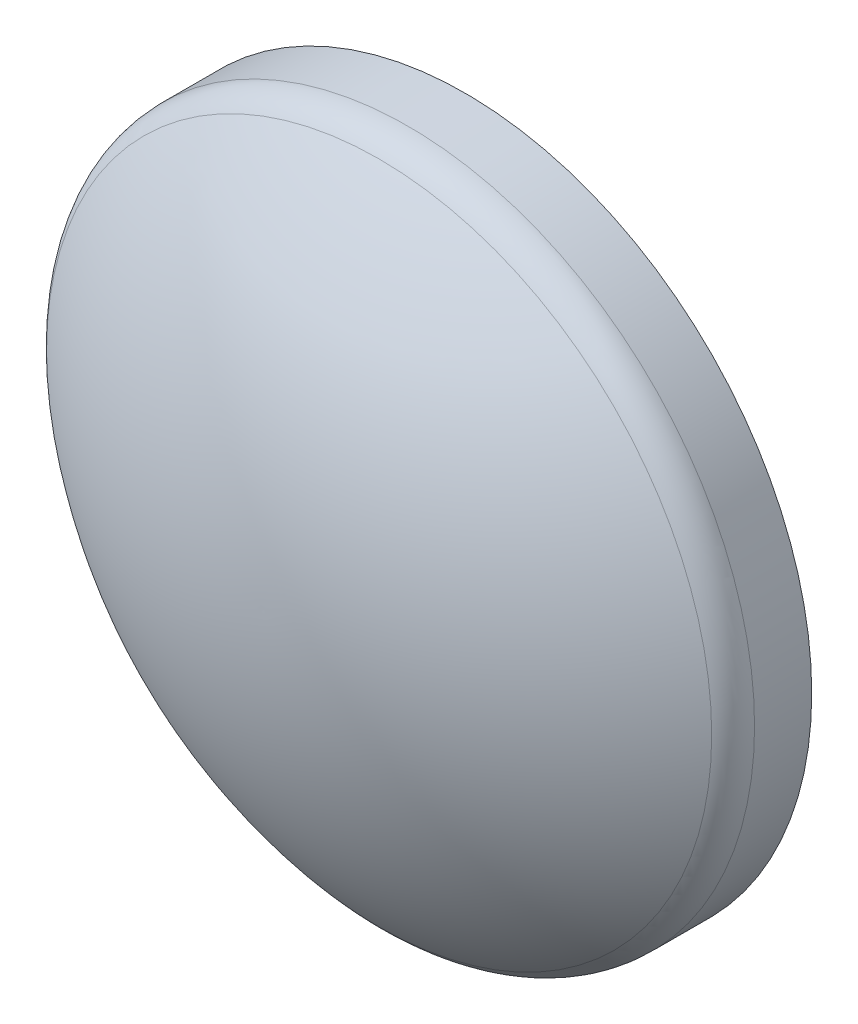
SolidWorks part; units mm, degrees
material "ASTM A240 304H"
ref_plane "Front Plane" through (0, 0, 0) normal (0, 0, 1) x (1, 0, 0)
ref_plane "Top Plane" through (0, 0, 0) normal (0, 1, 0) x (1, 0, 0)
ref_plane "Right Plane" through (0, 0, 0) normal (1, 0, 0) x (0, 0, -1)
ref_axis "Axis1" through (0, 0, -88.99) along (0, 0, 1)
ref_plane "Plane1" through (0, 0, 0) normal (1, 0, 0) x (0, 0, -1)
sketch "Sketch1" plane through (0, 0, 0) normal (1, 0, 0) x (0, 0, -1)
  line L0 (-12.7, 0) -> (12.7, 0) construction
  line L2 (-12.7, 215.011) -> (12.7, 215.011)
  line L3 (-12.7, 215.011) -> (-12.7, 230.886)
  line L4 (-12.7, 230.886) -> (12.7, 230.886)
  line L5 (12.7, 215.011) -> (12.7, 230.886)
  dimension "D1" = 215.011
  dimension "WIDTH" = 25.4
  dimension "THK" = 15.875
revolve "Revolve1" add sketch "Sketch1" angle 360 mid plane about L0
sketch "Sketch3" plane through (0, 0, 12.7) normal (0, 0, 1) x (1, 0, 0)
  circle A0 centre (0, 0) radius 230.886
  dimension "D1" = 461.772
sketch "Sketch4" plane through (0, 0, 0) normal (1, 0, 0) x (0, 0, -1)
  line L0 (-12.7, 0) -> (-140.4532, 0) construction
  line L1 (-12.7, 230.886) -> (-12.7, -230.886) construction
  line L2 (88.99, 0) -> (-88.99, 0) construction
  line L3 (-122.2825, 0) -> (-12.7, 0)
  line L4 (-12.7, -230.886) -> (-25.4, -230.886)
  line L6 (-12.7, -230.886) -> (-12.7, 0)
  arc A0 (-44.7323, -221.6444) -> (-122.2825, 0) centre (227.4353, -2.0278) cw
  arc A2 (-25.4, -230.886) -> (-44.7323, -221.6444) centre (-25.4, -206.0448) cw
  dimension "D2" = 12.7
revolve "Revolve2" add sketch "Sketch4" angle 360 mid plane about L0
shell "Shell1" thickness 15.875 removed face at (215.011, 0, 12.7)
